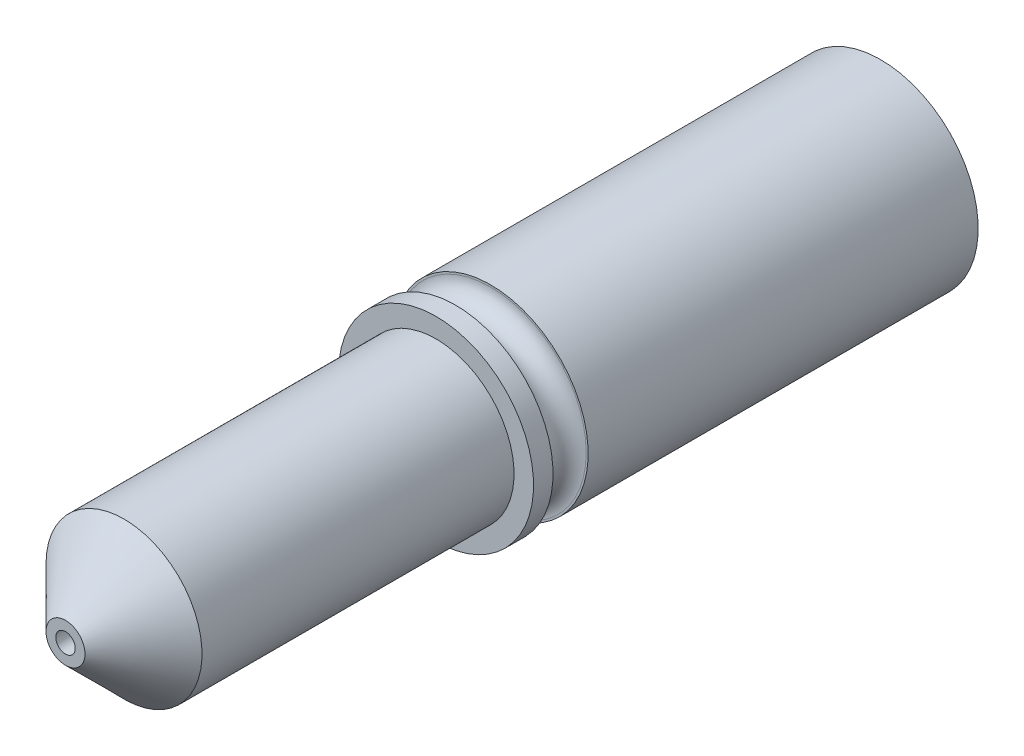
SolidWorks part; units mm, degrees
ref_plane "Front Plane" through (0, 0, 0) normal (0, 0, 1) x (1, 0, 0)
ref_plane "Top Plane" through (0, 0, 0) normal (0, 1, 0) x (1, 0, 0)
ref_plane "Right Plane" through (0, 0, 0) normal (1, 0, 0) x (0, 0, -1)
sketch "Sketch1" plane through (0, 0, 0) normal (0, 1, 0) x (1, 0, 0)
  line L0 (0, 0) -> (0, -20.6739) construction
  line L1 (0.25, -20.9) -> (0.5, -20.9)
  line L2 (0.5, -20.9) -> (2, -19.4)
  line L3 (2, -19.4) -> (2, -11.4)
  line L4 (2, -11.4) -> (2.5, -11.4)
  line L5 (2.5, -11.4) -> (2.5, -10.9)
  line L6 (2.5, -10.9) -> (2.45, -10.9)
  line L7 (1.65, 0) -> (1.65, -9.8)
  line L8 (2.45, -10) -> (2.5, -10)
  line L9 (2.5, -10) -> (2.5, 0)
  line L10 (2.5, 0) -> (1.65, 0)
  line L11 (1.65, -9.8) -> (1, -9.8)
  line L12 (1, -9.8) -> (1, -19.55)
  line L13 (1, -19.55) -> (0.25, -20.3)
  line L14 (0.25, -20.3) -> (0.25, -20.9)
  arc A0 (2.45, -10) -> (2.45, -10.9) centre (2.45, -10.45) ccw
  point P9 (2, -10.45)
  dimension "D1" = 5
  dimension "D2" = 3.3
  dimension "D3" = 2
  dimension "D4" = 0.5
  dimension "D5" = 4
  dimension "D6" = 1
  dimension "D7" = 9.8
  dimension "D8" = 0.9
  dimension "D9" = 10
  dimension "D10" = 0.5
  dimension "D11" = 45
  dimension "D12" = 0.6
  dimension "D13" = 8
  dimension "D14" = 45
revolve "Revolve1" add sketch "Sketch1" angle 360 about L0
